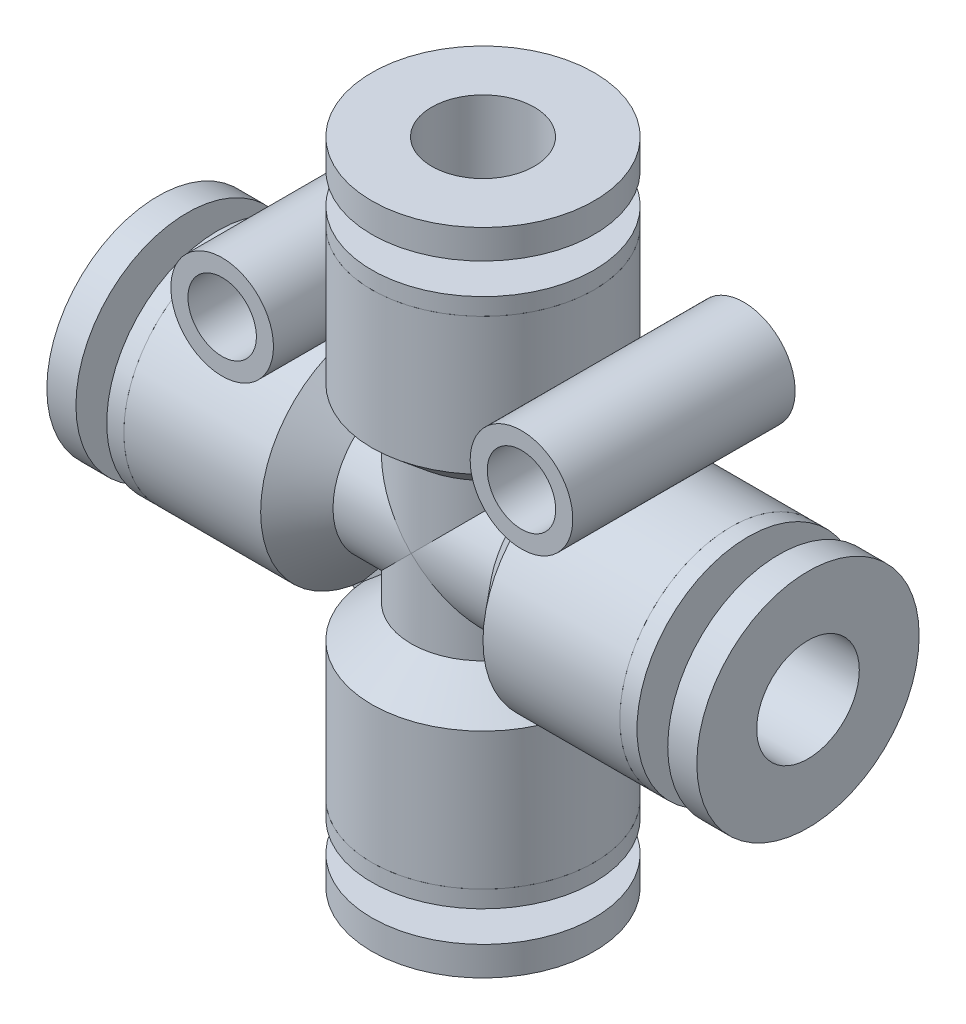
SolidWorks part; units mm, degrees
material "ABS"
ref_plane "Front" through (0, 0, 0) normal (0, 0, 1) x (1, 0, 0)
ref_plane "Top" through (0, 0, 0) normal (0, 1, 0) x (1, 0, 0)
ref_plane "Right" through (0, 0, 0) normal (1, 0, 0) x (0, 0, -1)
sketch "Esquisse1" plane through (0, 0, 0) normal (0, 0, 1) x (1, 0, 0)
  line L0 (-4.2, 4.5701) -> (-4.2, 0)
  line L1 (-4.2, 0) -> (-1.5, 0)
  line L2 (-1.5, 0) -> (-1.5, 3.5)
  line L3 (-1.5, 3.5) -> (-3, 3.5)
  line L4 (-3, 3.5) -> (-3, 14.5)
  line L5 (-3, 14.5) -> (-6.5, 14.5)
  line L6 (-6.5, 14.5) -> (-6.5, 6.5)
  line L7 (-6.5, 6.5) -> (-4.2, 4.5701)
  line L8 (0, 0) -> (0, 14.5) construction
  dimension "D1" = 14.5
  dimension "D2" = 13
  dimension "D3" = 2.3
  dimension "D4" = 6
  dimension "D5" = 11
  dimension "D6" = 50
  dimension "D7" = 8
  dimension "D8" = 3
revolve "Révolution1" add sketch "Esquisse1" angle 360 about L8
ref_axis "Axe1" through (0, 0, -80.9) along (0, 0, 1)
sketch "Esquisse2" plane through (0, 0, 0) normal (0, 0, 1) x (1, 0, 0)
  line L0 (0, 0) -> (-6.5, 0)
  line L1 (-6.5, 0) -> (-6.5, 6.5)
  line L2 (-6.5, 6.5) -> (0, 0)
  line L3 (-6.5, 14.5) -> (-6.5, 6.5) construction
extrude "Enlèv. mat.-Extru.1" cut sketch "Esquisse2" against normal through all both and the other way through all
mirror "Symétrie1" about plane through (0, 0, 0) normal (1, 0, 0) of "Enlèv. mat.-Extru.1"
sketch "Esquisse3" plane through (0, 0, 0) normal (0, 0, 1) x (1, 0, 0)
  line L0 (-3, 3) -> (-7.0711, 7.0711)
  line L1 (-7.0711, 7.0711) -> (-4, 10.1421)
  line L2 (-4, 10.1421) -> (-3, 10.1421)
  line L10 (-4.2, 4.2) -> (0, 0) construction
  line L11 (-4.2, 4.2) -> (0, 0) construction
  line L12 (-3, 3) -> (-3, 10.1421)
  line L13 (-3, 3.5) -> (-3, 14.5) construction
  line L14 (0, -50) -> (0, 50) construction
  line L15 (3, 3) -> (7.0711, 7.0711)
  line L16 (3, 3) -> (3, 10.1421)
  line L17 (4, 10.1421) -> (3, 10.1421)
  line L18 (7.0711, 7.0711) -> (4, 10.1421)
  dimension "D1" = 10
  dimension "D2" = 1
extrude "Boss.-Extru.1" add sketch "Esquisse3" along normal mid plane 1
mirror "Symétrie2" about plane through (-6.5, 6.5, -6.5) normal (0.7071, 0.7071, 0) of bodies 107
mirror "Symétrie3" about plane through (6.5, 6.5, -6.5) normal (0.7071, -0.7071, 0) of bodies 108
sketch "Esquisse4" plane through (0, 0, 0) normal (0, 0, 1) x (1, 0, 0)
  line L0 (0, -50) -> (0, 50) construction
  line L1 (-4.1701, 4.1701) -> (0, 0) construction
  circle A0 centre (-8.75, 8.75) radius 2
  circle A1 centre (-8.75, 8.75) radius 3
  circle A2 centre (8.75, 8.75) radius 3
  circle A3 centre (8.75, 8.75) radius 2
  dimension "D1" = 6
  dimension "D2" = 4
  dimension "D3" = 17.5
  dimension "D4" = 8.75
extrude "Boss.-Extru.2" add sketch "Esquisse4" along normal mid plane 13
sketch "Esquisse6" plane through (0, 0, 0) normal (0, 0, 1) x (1, 0, 0)
  line L0 (-6.5, 14.5) -> (-6.5, 6.5) construction
  line L1 (-6.5, 19) -> (-3, 19)
  line L2 (-6.5, 19) -> (-6.5, 17.3)
  line L3 (-3.5, 14.5) -> (-3, 14.5)
  line L4 (-3, 19) -> (-3, 14.5)
  line L8 (-6.5, 17.3) -> (-3.5, 17.3)
  line L9 (-3.5, 14.5) -> (-3.5, 17.3)
  dimension "D1" = 19
  dimension "D2" = 3
  dimension "D3" = 1.7
revolve "Révolution2" add sketch "Esquisse6" angle 360 about L8
sketch "Esquisse7" plane through (0, 14.5, 0) normal (0, 1, 0) x (1, 0, 0)
  circle A0 centre (0, 0) radius 6.5 construction
  circle A1 centre (0, 0) radius 3.5 construction
  circle A2 centre (0, 0) radius 6.5
  circle A3 centre (0, 0) radius 3.5
extrude "Boss.-Extru.4" add sketch "Esquisse7" along normal blind 1 separate body
pattern_circular "Répétition circulaire3" count 4 over 360 about axis through (0, 0, -80.9) along (0, 0, 1) of bodies 112 113
